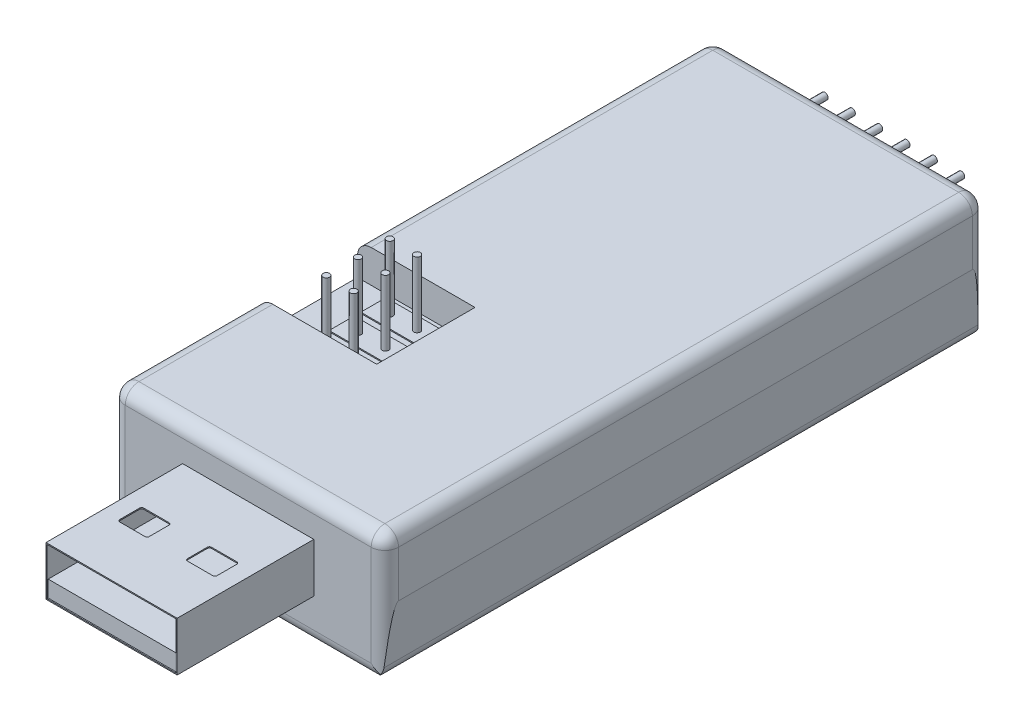
SolidWorks part; units mm, degrees
ref_plane "Front Plane" through (0, 0, 0) normal (0, 0, 1) x (1, 0, 0)
ref_plane "Top Plane" through (0, 0, 0) normal (0, 1, 0) x (1, 0, 0)
ref_plane "Right Plane" through (0, 0, 0) normal (1, 0, 0) x (0, 0, -1)
sketch "Sketch1" plane through (0, 0, 0) normal (0, 0, 1) x (1, 0, 0)
  line L0 (-12.5, 0) -> (-12, -6.2)
  line L5 (-12.5, 5.5) -> (12.5, 5.5)
  line L6 (-12.5, 5.5) -> (-12.5, 0)
  line L7 (-12, -6.2) -> (12, -6.2)
  line L8 (12.5, 5.5) -> (12.5, 0)
  line L9 (12.5, 0) -> (12, -6.2)
  point P13 (6.75, 3.425)
  point P18 (-6.75, 3.425)
  dimension "D7" = 0.5
  dimension "D1" = 25
  dimension "D2" = 13.5
  dimension "D3" = 6.75
  dimension "D4" = 11.7
  dimension "D5" = 5.5
  dimension "D6" = 12.5
  dimension "D8" = 0.5
extrude "Boss-Extrude1" add sketch "Sketch1" against normal blind 55
sketch "Sketch2" plane through (0, 0, 0) normal (0, 0, 1) x (1, 0, 0)
  line L1 (-6, 2.25) -> (6, 2.25)
  line L2 (-6, 2.25) -> (-6, -2.25)
  line L3 (-6, -2.25) -> (6, -2.25)
  line L4 (6, 2.25) -> (6, -2.25)
  line L5 (-5.9, 2.15) -> (5.9, 2.15)
  line L6 (-5.9, 2.15) -> (-5.9, -2.15)
  line L7 (-5.9, -2.15) -> (5.9, -2.15)
  line L8 (5.9, 2.15) -> (5.9, -2.15)
  dimension "D1" = 12
  dimension "D2" = 6
  dimension "D3" = 4.5
  dimension "D4" = 2.25
  dimension "D5" = 0.1
  dimension "D6" = 0.1
  dimension "D7" = 0.1
  dimension "D8" = 0.1
extrude "Boss-Extrude2" add sketch "Sketch2" along normal blind 12.5
sketch "Sketch3" plane through (0, 0, 0) normal (0, 0, 1) x (1, 0, 0)
  line L0 (5.9, -2.15) -> (5.9, 2.15) construction
  line L1 (-5.9, -2.15) -> (5.9, -2.15)
  line L2 (-5.9, -2.15) -> (-5.9, -0.65)
  line L3 (-5.9, -0.65) -> (5.9, -0.65)
  line L4 (5.9, -2.15) -> (5.9, -0.65)
  dimension "D1" = 1.5
extrude "Boss-Extrude3" add sketch "Sketch3" along normal blind 12.4
sketch "Sketch4" plane through (0, 2.25, 0) normal (0, 1, 0) x (1, 0, 0)
  line L1 (-4.25, -5.3) -> (-1.95, -5.3)
  line L2 (-4.45, -5.5) -> (-4.45, -7.3)
  line L3 (-4.25, -7.5) -> (-1.95, -7.5)
  line L4 (-1.75, -5.5) -> (-1.75, -7.3)
  line L5 (1.95, -5.3) -> (4.25, -5.3)
  line L6 (1.75, -5.5) -> (1.75, -7.3)
  line L7 (1.95, -7.5) -> (4.25, -7.5)
  line L8 (4.45, -5.5) -> (4.45, -7.3)
  arc A0 (4.25, -7.5) -> (4.45, -7.3) centre (4.25, -7.3) ccw
  arc A1 (4.25, -5.3) -> (4.45, -5.5) centre (4.25, -5.5) cw
  arc A2 (1.75, -7.3) -> (1.95, -7.5) centre (1.95, -7.3) ccw
  arc A3 (1.95, -5.3) -> (1.75, -5.5) centre (1.95, -5.5) ccw
  arc A4 (-4.45, -7.3) -> (-4.25, -7.5) centre (-4.25, -7.3) ccw
  arc A5 (-1.95, -7.5) -> (-1.75, -7.3) centre (-1.95, -7.3) ccw
  arc A6 (-1.95, -5.3) -> (-1.75, -5.5) centre (-1.95, -5.5) cw
  arc A7 (-4.25, -5.3) -> (-4.45, -5.5) centre (-4.25, -5.5) ccw
  point P13 (4.45, -5.3)
  point P16 (1.75, -7.5)
  point P19 (1.75, -5.3)
  point P22 (-4.45, -7.5)
  point P27 (-1.75, -5.3)
  point P30 (-4.45, -5.3)
  dimension "D9" = 0.2
  dimension "D1" = 2.7
  dimension "D2" = 2.7
  dimension "D3" = 2.2
  dimension "D4" = 2.2
  dimension "D5" = 3.5
  dimension "D6" = 1.75
  dimension "D7" = 5.3
  dimension "D8" = 5.3
extrude "Cut-Extrude1" cut sketch "Sketch4" against normal blind 0.5
sketch "Sketch6" plane through (0, 5.5, 0) normal (0, 1, 0) x (1, 0, 0)
  line L0 (-12.5, 55) -> (-12.5, 0) construction
  line L1 (-12.5, 13.5) -> (-1.75, 13.5)
  line L2 (-12.5, 13.5) -> (-12.5, 22.5)
  line L3 (-12.5, 22.5) -> (-1.75, 22.5)
  line L4 (-1.75, 13.5) -> (-1.75, 22.5)
  line L5 (12.5, 0) -> (-12.5, 0) construction
  dimension "D1" = 10.75
  dimension "D2" = 9
  dimension "D3" = 13.5
extrude "Cut-Extrude2" cut sketch "Sketch6" against normal blind 3
sketch "Sketch7" plane through (0, 2.5, 0) normal (0, 1, 0) x (1, 0, 0)
  line L0 (-12.5, 22.5) -> (-12.5, 13.5) construction
  line L1 (-9.5, 16.3) -> (-4, 16.3)
  line L2 (-9.5, 16.3) -> (-9.5, 14)
  line L3 (-9.5, 14) -> (-4, 14)
  line L4 (-4, 16.3) -> (-4, 14)
  line L5 (-12.5, 13.5) -> (-1.75, 13.5) construction
  dimension "D1" = 3
  dimension "D2" = 5.5
  dimension "D3" = 2.3
  dimension "D4" = 0.5
extrude "Boss-Extrude4" add sketch "Sketch7" along normal blind 0.1
sketch "Sketch8" plane through (0, 2.6, 0) normal (0, 1, 0) x (1, 0, 0)
  line L0 (-4, 16.3) -> (-9.5, 16.3) construction
  line L2 (-4, 16.3) -> (-9.5, 16.3) construction
  line L3 (-9.5, 14) -> (-4, 14) construction
  circle A0 centre (-8, 15.15) radius 0.3
  circle A1 centre (-5.5, 15.15) radius 0.3
  point P10 (-6.75, 14)
  dimension "D1" = 0.6
  dimension "D2" = 0.6
  dimension "D4" = 1.15
  dimension "D5" = 2.5
  dimension "D6" = 1.25
  dimension "D3" = 1.15
extrude "Boss-Extrude5" add sketch "Sketch8" along normal blind 6
pattern_linear "LPattern1" count 3 spacing 2.9 along (0, 0, -1) of "Boss-Extrude4", "Boss-Extrude5"
sketch "Sketch9" plane through (0, 0, -55) normal (0, 0, -1) x (-1, 0, 0)
  line L0 (-12.5, 5.5) -> (12.5, 5.5) construction
  line L1 (-7.75, 3.5) -> (7.75, 3.5)
  line L2 (-7.75, 3.5) -> (-7.75, 0)
  line L3 (-7.75, 0) -> (7.75, 0)
  line L4 (7.75, 3.5) -> (7.75, 0)
  dimension "D1" = 15.5
  dimension "D2" = 3.5
  dimension "D3" = 2
  dimension "D4" = 7.75
extrude "Cut-Extrude3" cut sketch "Sketch9" against normal blind 2
sketch "Sketch10" plane through (0, 0, -53) normal (0, 0, -1) x (-1, 0, 0)
  line L1 (7.75, 3.5) -> (-7.75, 3.5) construction
  line L2 (-7.75, 3.5) -> (-7.75, 0) construction
  circle A0 centre (-6.25, 1.75) radius 0.3
  dimension "D1" = 1.75
  dimension "D2" = 1.5
extrude "Boss-Extrude6" add sketch "Sketch10" along normal blind 6
pattern_linear "LPattern2" count 6 spacing 2.5 along (-1, 0, 0) of "Boss-Extrude6"
fillet "Fillet1" radius 1.25 13 edges at (0, -6.2, 0) (0, 5.5, 0) (-12.5, 5.5, -6.75) (-12.5, 5.5, -38.75) (-12, -6.2, -27.5) (12, -6.2, -27.5) (0, -6.2, -55) (0, 5.5, -55) (12.5, 5.5, -27.5) (12.5, 2.75, -55) (-12.5, 2.75, -55) (-12.5, 2.75, 0) (12.5, 2.75, 0)
